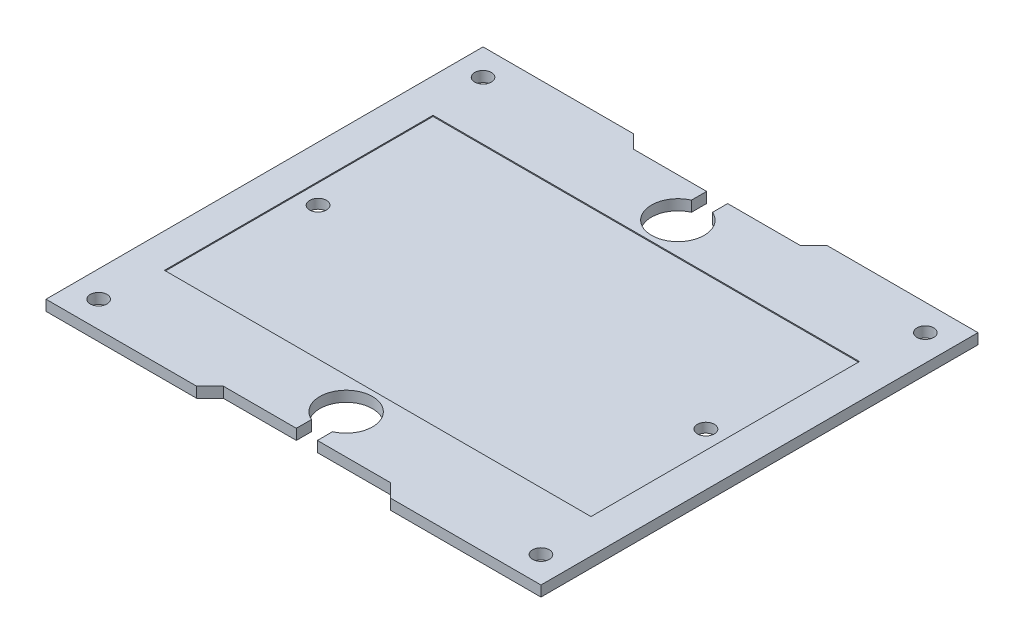
SolidWorks part; units mm, degrees
ref_plane "Front Plane" through (0, 0, 0) normal (0, 0, 1) x (1, 0, 0)
ref_plane "Top Plane" through (0, 0, 0) normal (0, 1, 0) x (1, 0, 0)
ref_plane "Right Plane" through (0, 0, 0) normal (1, 0, 0) x (0, 0, -1)
sketch "Sketch1" plane through (0, 0, 0) normal (0, 1, 0) x (1, 0, 0)
  line L1 (-47, -41.5) -> (47, -41.5)
  line L2 (-47, -41.5) -> (-47, 41.5)
  line L3 (-47, 41.5) -> (47, 41.5)
  line L4 (47, -41.5) -> (47, 41.5)
  line L5 (-47, -41.5) -> (47, 41.5) construction
  line L6 (-47, 41.5) -> (47, -41.5) construction
  line L7 (-42, -36.5) -> (42, -36.5) construction
  line L8 (-42, -36.5) -> (-42, 36.5) construction
  line L9 (-42, 36.5) -> (42, 36.5) construction
  line L10 (42, -36.5) -> (42, 36.5) construction
  line L11 (-42, -36.5) -> (42, 36.5) construction
  line L12 (-42, 36.5) -> (42, -36.5) construction
  circle A0 centre (-42, 36.5) radius 1.5875
  circle A1 centre (42, 36.5) radius 1.5875
  circle A2 centre (42, -36.5) radius 1.5875
  circle A3 centre (-42, -36.5) radius 1.5875
  point P0 (0, 0)
  point P14 (0, 0)
  dimension "D3" = 3.175
  dimension "D1" = 83
  dimension "D2" = 94
  dimension "D4" = 5
  dimension "D5" = 5
extrude "Boss-Extrude1" add sketch "Sketch1" along normal blind 2
sketch "Sketch2" plane through (0, 2, 0) normal (0, 1, 0) x (1, 0, 0)
  line L0 (-42, -36.5) -> (42, 36.5) construction
  line L1 (-40.5, 25.5) -> (40.5, 25.5)
  line L2 (-40.5, 25.5) -> (-40.5, -25.5)
  line L3 (-40.5, -25.5) -> (40.5, -25.5)
  line L4 (40.5, 25.5) -> (40.5, -25.5)
  line L5 (-40.5, 25.5) -> (40.5, -25.5) construction
  line L6 (-40.5, -25.5) -> (40.5, 25.5) construction
  line L7 (42, -36.5) -> (-42, 36.5) construction
  point P4 (0, 0)
  point P11 (0, 0)
  dimension "D1" = 81
  dimension "D2" = 51
extrude "Cut-Extrude1" cut sketch "Sketch2" against normal blind 0.2
sketch "Sketch3" plane through (0, 2, 0) normal (0, 1, 0) x (1, 0, 0)
  line L0 (-40.5, 0) -> (40.5, 0) construction
  line L1 (-40.5, 25.5) -> (-40.5, -25.5) construction
  line L2 (40.5, -25.5) -> (40.5, 25.5) construction
  line L3 (47, 41.5) -> (-47, 41.5) construction
  line L4 (-2.1788, 41.5) -> (2.1788, 41.5)
  line L5 (-2, 38.96) -> (-2, 36.0826)
  line L7 (2, 38.96) -> (2, 36.0826)
  line L8 (-2.1788, 41.5) -> (2, 36.0826) construction
  line L9 (-2, 36.0826) -> (2.1788, 41.5) construction
  line L10 (-47, -41.5) -> (47, -41.5) construction
  line L11 (-2.1788, -41.5) -> (2.1788, -41.5)
  line L12 (-2, -38.96) -> (-2, -36.0826)
  line L14 (2, -38.96) -> (2, -36.0826)
  line L15 (-2.1788, -41.5) -> (2, -36.0826) construction
  line L16 (-2, -36.0826) -> (2.1788, -41.5) construction
  line L17 (0, 31.5) -> (0, -57.1079) construction
  line L18 (-18.415, -41.5) -> (-15.875, -38.96)
  line L19 (-15.875, -38.96) -> (-2, -38.96)
  line L20 (15.875, -38.96) -> (18.415, -41.5)
  line L21 (2, -38.96) -> (15.875, -38.96)
  line L22 (-0.2196, -38.96) -> (0.2196, -38.96)
  line L23 (-18.415, 41.5) -> (-15.875, 38.96)
  line L24 (-15.875, 38.96) -> (-2, 38.96)
  line L25 (15.875, 38.96) -> (18.415, 41.5)
  line L26 (2, 38.96) -> (15.875, 38.96)
  line L27 (0, 31.5) -> (0, 45.3262) construction
  line L28 (-18.415, 41.5) -> (18.415, 41.5)
  line L29 (18.415, -41.5) -> (-18.415, -41.5)
  circle A0 centre (-36.83, 0) radius 1.6
  circle A1 centre (36.83, 0) radius 1.6
  arc A2 (2, -36.0826) -> (-2, -36.0826) centre (0, -31.5) ccw
  arc A3 (-2, 36.0826) -> (2, 36.0826) centre (0, 31.5) ccw
  point P19 (0, 38.6754)
  point P26 (0, -38.6754)
  line M13 (47, 41.5) -> (-47, 41.5)
  dimension "D1" = 3.2
  dimension "D5" = 10
  dimension "D2" = 73.66
  dimension "D3" = 36.83
  dimension "D4" = 4
  dimension "D6" = 10
  dimension "D7" = 10
  dimension "D8" = 2.54
  dimension "D9" = 45
  dimension "D10" = 45
  dimension "D11" = 31.75
  dimension "D12" = 15.875
  dimension "D13" = 45
  dimension "D14" = 45
  dimension "D15" = 4
extrude "Cut-Extrude2" cut sketch "Sketch3" against normal through all contours A0 | A1 | L14 A2 L12 L19 L18 L20 L21 | L5 A3 L7 L26 L25 L23 L24 M13 region at (0, 2, -36.1985) region at (0, 2, 36.1985) region at (-36.83, 2, 0) region at (36.83, 2, 0)
equation "\"D5@Sketch1\"=\"D4@Sketch1\""
equation "\"D3@Sketch3\"=\"D2@Sketch3\"/2"
equation "\"D12@Sketch3\"=\"D11@Sketch3\"/2"
equation "\"D14@Sketch3\"=\"D13@Sketch3\""
equation "\"D15@Sketch3\"=\"D4@Sketch3\""
